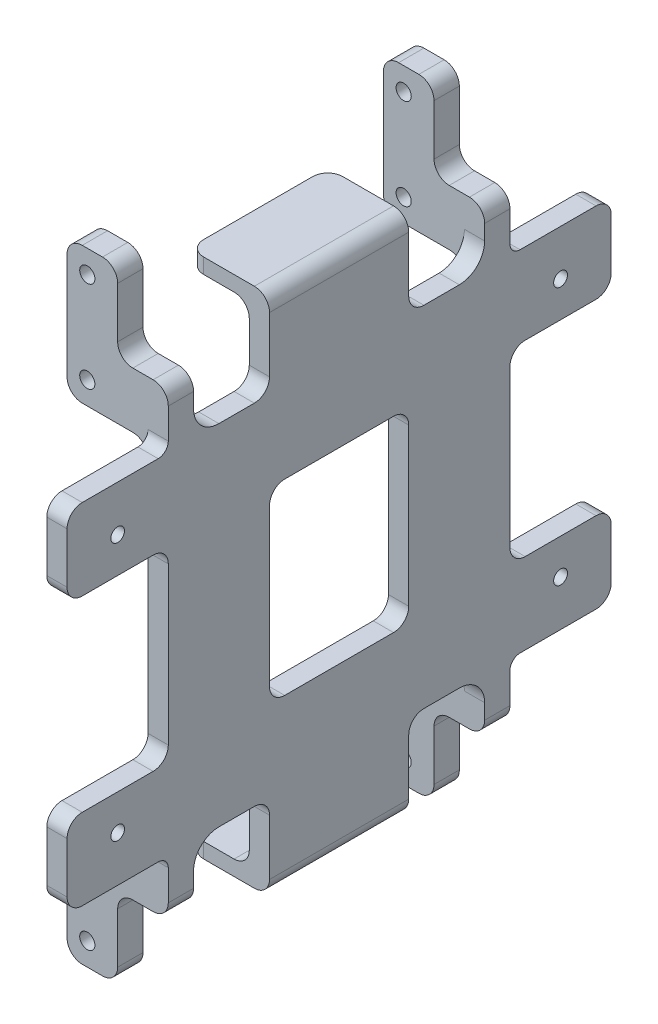
SolidWorks part; units mm, degrees
ref_plane "Front Plane" through (0, 0, 0) normal (0, 0, 1) x (1, 0, 0)
ref_plane "Top Plane" through (0, 0, 0) normal (0, 1, 0) x (1, 0, 0)
ref_plane "Right Plane" through (0, 0, 0) normal (1, 0, 0) x (0, 0, -1)
sketch "Sketch9" plane through (47.2641, 0, 0) normal (-1, 0, 0) x (0, 0, 1)
  line L0 (5, 63.5) -> (5, 4.5) construction
  line L1 (-107.5, -0.5) -> (-67.5, -0.5)
  line L2 (-107.5, -0.5) -> (-107.5, 15.5)
  line L3 (-107.5, 15.5) -> (0, 15.5)
  line L4 (0, -0.5) -> (0, 15.5)
  line L5 (-112.5, 4.5) -> (-112.5, 63.5) construction
  line L6 (-31.25, -17.5) -> (-76.25, -17.5) construction
  line L8 (-67.5, -0.5) -> (-67.5, -17.5)
  line L9 (-67.5, -17.5) -> (-40, -17.5)
  line L10 (-40, -0.5) -> (-40, -17.5)
  line L11 (-40, -0.5) -> (0, -0.5)
  dimension "D1" = 16
  dimension "D2" = 5
  dimension "D3" = 5
  dimension "D4" = 40
  dimension "D5" = 40
extrude "Boss-Extrude4" add sketch "Sketch9" along normal blind 4
sketch "Sketch10" plane through (0, 0, -20) normal (0, 0, -1) x (-1, 0, 0)
  line L0 (-43.2641, -0.5) -> (-43.2641, 15.5) construction
  line L1 (-43.2641, -0.5) -> (-27.2641, -0.5)
  line L2 (-47.2641, 7.5) -> (-47.2641, -11.5)
  line L3 (-37.2641, -27.5) -> (-27.2641, -27.5)
  line L4 (-27.2641, -0.5) -> (-27.2641, -27.5)
  line L5 (-43.2641, -0.5) -> (-43.2641, 7.5)
  line L6 (-43.2641, 7.5) -> (-47.2641, 7.5)
  line L7 (-47.2641, -11.5) -> (-37.2641, -11.5)
  line L8 (-37.2641, -27.5) -> (-37.2641, -11.5)
  dimension "D1" = 16
  dimension "D2" = 10
  dimension "D3" = 27
extrude "Boss-Extrude5" add sketch "Sketch10" along normal blind 5
ref_plane "Plane1" through (0, 0, -53.75) normal (0, 0, 1) x (1, 0, 0)
mirror "Mirror1" about plane through (0, 0, -53.75) normal (0, 0, 1) of "Boss-Extrude5"
fillet "Fillet5" radius 5 2 edges at (45.2641, -0.5, -82.5) (45.2641, -0.5, -25)
fillet "Fillet6" radius 2 2 edges at (45.2641, -0.5, -87.5) (45.2641, -0.5, -20)
fillet "Fillet7" radius 3 16 edges at (45.2641, 15.5, -107.5) (45.2641, -0.5, -107.5) (45.2641, 15.5, 0) (43.2641, -0.5, -85) (37.2641, -11.5, -85) (47.2641, -11.5, -85) (27.2641, -0.5, -85) (37.2641, -27.5, -85) (27.2641, -27.5, -85) (47.2641, -11.5, -22.5) (37.2641, -11.5, -22.5) (43.2641, -0.5, -22.5) (27.2641, -0.5, -22.5) (37.2641, -27.5, -22.5) (27.2641, -27.5, -22.5) (45.2641, -0.5, 0)
sketch "Sketch11" plane through (0, 0, -87.5) normal (0, 0, -1) x (-1, 0, 0)
  circle A0 centre (-31.2641, -5) radius 1.5 construction
  circle A1 centre (-31.2641, -23) radius 1.5 construction
  circle A2 centre (-31.2641, -5) radius 1.5
  circle A3 centre (-31.2641, -23) radius 1.5
extrude "Cut-Extrude6" cut sketch "Sketch11" against normal through all
sketch "Sketch12" plane through (43.2641, 0, 0) normal (-1, 0, 0) x (0, 0, 1)
  circle A0 centre (-97.5, 8.5) radius 1.368
  circle A1 centre (-10, 8.5) radius 1.35
extrude "Cut-Extrude7" cut sketch "Sketch12" against normal blind 5
fillet "Fillet8" radius 3 2 edges at (45.2641, -0.5, -67.5) (45.2641, -0.5, -40)
sketch "Sketch13" plane through (43.2641, 0, 0) normal (-1, 0, 0) x (0, 0, 1)
  line L1 (-40, -17.5) -> (-67.5, -17.5)
  line L2 (-40, -17.5) -> (-40, -14.5)
  line L3 (-40, -14.5) -> (-67.5, -14.5)
  line L4 (-67.5, -17.5) -> (-67.5, -14.5)
  dimension "D1" = 3
extrude "Boss-Extrude6" add sketch "Sketch13" along normal blind 12
fillet "Fillet9" radius 3 4 edges at (31.2641, -16, -40) (31.2641, -16, -67.5) (43.2641, -14.5, -53.75) (47.2641, -17.5, -53.75)
sketch "Sketch14" plane through (47.2641, 0, 0) normal (-1, 0, 0) x (0, 0, 1)
  line L0 (5, 34) -> (-112.5, 34) construction
  line L1 (5, 63.5) -> (5, 4.5) construction
  line L2 (-112.5, 4.5) -> (-112.5, 63.5) construction
  line L3 (-3, 15.5) -> (-104.5, 15.5) construction
  line L4 (-20, 15.5) -> (-40, 15.5)
  line L5 (-20, 15.5) -> (-20, 34)
  line L6 (-20, 34) -> (-40, 34)
  line L7 (-40, 15.5) -> (-40, 34)
  line L8 (-107.5, 12.5) -> (-107.5, 2.5) construction
  line L9 (-67.5, 15.5) -> (-87.5, 15.5)
  line L10 (-67.5, 15.5) -> (-67.5, 34)
  line L11 (-67.5, 34) -> (-87.5, 34)
  line L12 (-87.5, 15.5) -> (-87.5, 34)
  line L13 (0, 2.5) -> (0, 12.5) construction
  dimension "D1" = 20
  dimension "D2" = 20
  dimension "D3" = 20
  dimension "D4" = 20
extrude "Boss-Extrude7" add sketch "Sketch14" along normal blind 4
fillet "Fillet10" radius 3 4 edges at (45.2641, 15.5, -20) (45.2641, 15.5, -40) (45.2641, 15.5, -67.5) (45.2641, 15.5, -87.5)
mirror "Mirror2" about plane through (43.2641, 34, -20) normal (0, -1, 0) of bodies 121
